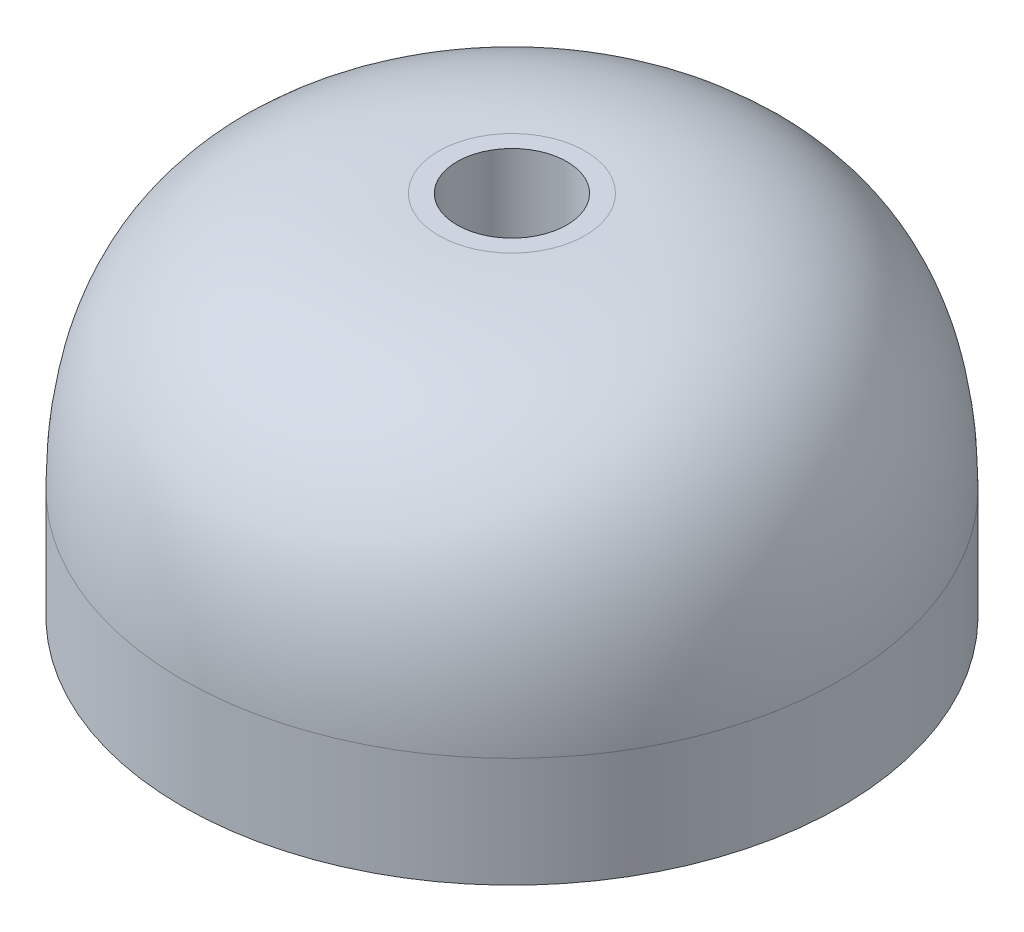
SolidWorks part; units mm, degrees
ref_plane "Płaszczyzna przednia" through (0, 0, 0) normal (0, 0, 1) x (1, 0, 0)
ref_plane "Płaszczyzna górna" through (0, 0, 0) normal (0, 1, 0) x (1, 0, 0)
ref_plane "Płaszczyzna prawa" through (0, 0, 0) normal (1, 0, 0) x (0, 0, -1)
sketch "Szkic1" plane through (0, 0, 0) normal (0, 1, 0) x (1, 0, 0)
  circle A0 centre (0, 0) radius 9
  dimension "D1" = 18
extrude "Dodanie-wyciągnięcie1" add sketch "Szkic1" along normal blind 10
fillet "Zaokrąglenie1" radius 7 1 edges at (0, 10, 9) conic rho 0.5
sketch "Szkic2" plane through (0, 0, 0) normal (0, 1, 0) x (1, 0, 0)
  circle A0 centre (0, 0) radius 1.5
  dimension "D1" = 3
extrude "Wytnij-wyciągnięcie1" cut sketch "Szkic2" along normal up to next
